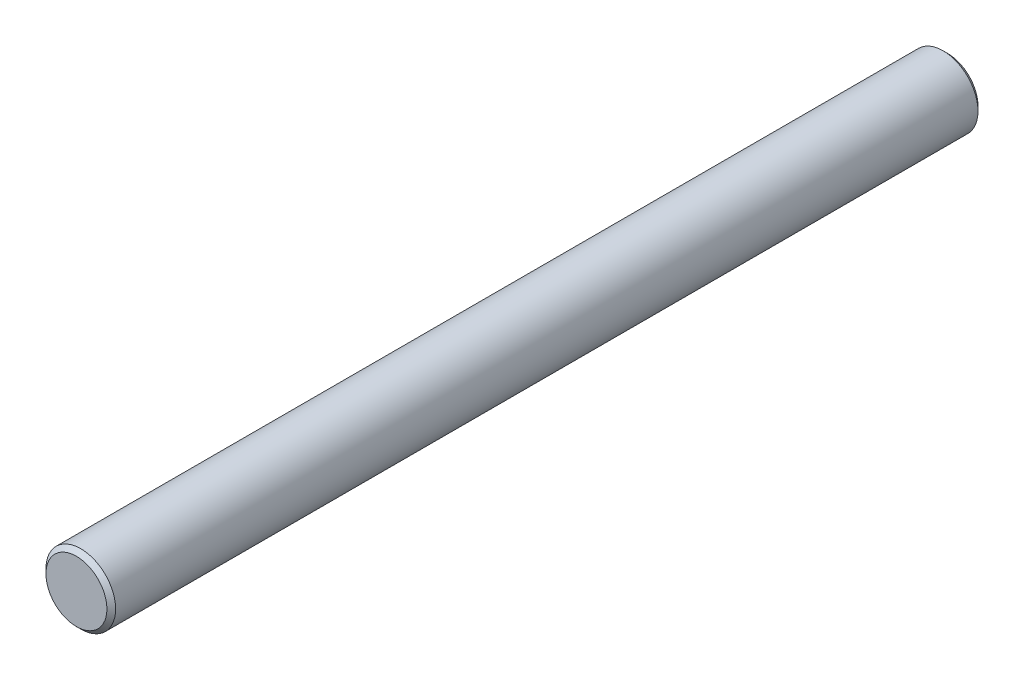
SolidWorks part; units mm, degrees
ref_plane "Alzado" through (0, 0, 0) normal (0, 0, 1) x (1, 0, 0)
ref_plane "Planta" through (0, 0, 0) normal (0, 1, 0) x (1, 0, 0)
ref_plane "Vista lateral" through (0, 0, 0) normal (1, 0, 0) x (0, 0, -1)
sketch "Croquis1" plane through (0, 0, 0) normal (0, 0, 1) x (1, 0, 0)
  circle A0 centre (0, 0) radius 4
  dimension "D1" = 8
extrude "Saliente-Extruir1" add sketch "Croquis1" against normal blind 100
chamfer "Chaflán1" distance 0.5 angle 45 2 edges at (4, 0, -100) (4, 0, 0)
